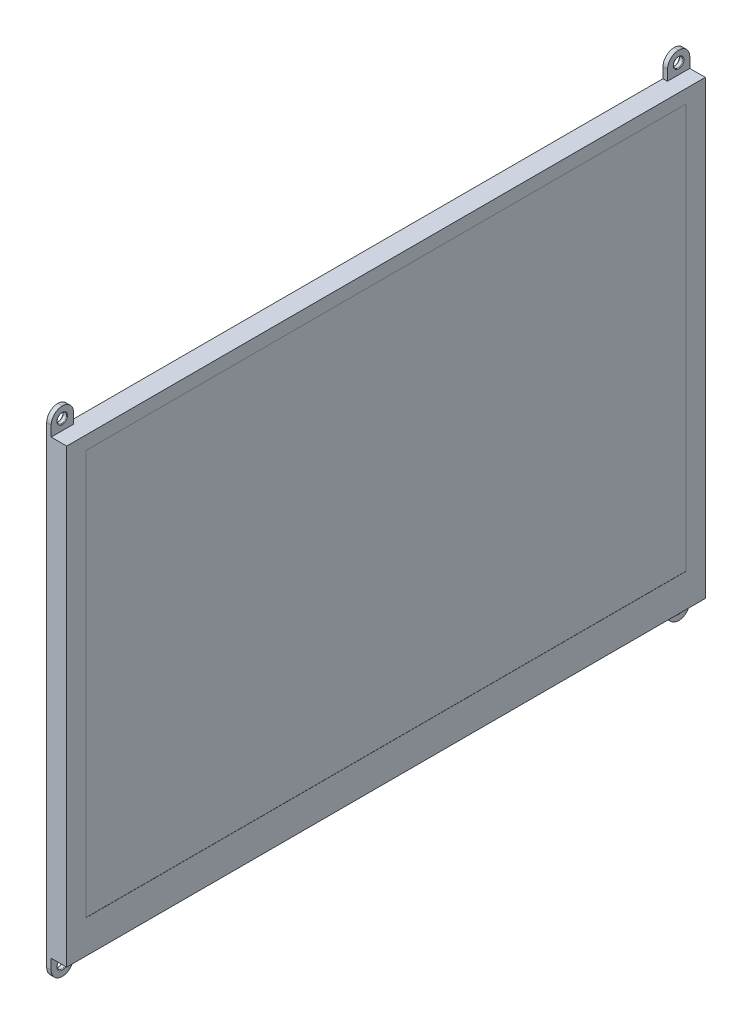
SolidWorks part; units mm, degrees
ref_plane "Front Plane" through (0, 0, 0) normal (1, 0, 0) x (0, 1, 0)
ref_plane "Top Plane" through (0, 0, 0) normal (0, 0, 1) x (0, 1, 0)
ref_plane "Right Plane" through (0, 0, 0) normal (0, 1, 0) x (-1, 0, 0)
sketch "Sketch1" plane through (0, 0, 0) normal (1, 0, 0) x (0, 1, 0)
  line L0 (0, 0) -> (0, 117.475) construction
  line L1 (-83.0199, -117.475) -> (83.0199, -117.475)
  line L2 (-83.0199, -117.475) -> (-83.0199, 117.475)
  line L3 (-83.0199, 117.475) -> (83.0199, 117.475)
  line L4 (83.0199, -117.475) -> (83.0199, 117.475)
  line L5 (-83.0199, -117.475) -> (83.0199, 117.475) construction
  line L6 (-83.0199, 117.475) -> (83.0199, -117.475) construction
  line L7 (83.0199, 117.475) -> (90.8939, 117.475)
  line L8 (83.0199, 117.475) -> (83.0199, 109.2708)
  line L9 (83.0199, 109.2708) -> (90.8939, 109.2708)
  line L10 (90.8939, 117.475) -> (90.8939, 109.2708)
  line L11 (83.0199, 117.475) -> (90.8939, 109.2708) construction
  line L12 (83.0199, 109.2708) -> (90.8939, 117.475) construction
  line L13 (0, 0) -> (83.0199, 0) construction
  line L14 (90.8939, 113.3729) -> (86.8939, 113.3729) construction
  line L15 (-83.0199, -117.475) -> (-83.0199, 117.475)
  line L16 (-83.0199, 117.475) -> (-90.8939, 117.475)
  line L17 (-83.0199, 109.2708) -> (-90.8939, 109.2708)
  line L18 (-90.8939, 117.475) -> (-90.8939, 109.2708)
  line L19 (-83.0199, 117.475) -> (-90.8939, 117.475)
  line L20 (-83.0199, 117.475) -> (-83.0199, 109.2708)
  line L21 (-90.8939, -109.2708) -> (-83.0199, -109.2708)
  line L22 (-90.8939, 117.475) -> (-83.0199, 117.475)
  line L23 (-90.8939, 117.475) -> (-90.8939, 109.2708)
  line L24 (-90.8939, 109.2708) -> (-83.0199, 109.2708)
  line L25 (-83.0199, 117.475) -> (-83.0199, 109.2708)
  line L26 (-90.8939, 117.475) -> (-83.0199, 109.2708) construction
  line L27 (-90.8939, 109.2708) -> (-83.0199, 117.475) construction
  line L28 (-83.0199, -117.475) -> (-83.0199, -109.2708)
  line L29 (-90.8939, -117.475) -> (-83.0199, -117.475)
  line L30 (-90.8939, -117.475) -> (-90.8939, -109.2708)
  line L31 (83.0199, -109.2708) -> (90.8939, -109.2708)
  line L32 (90.8939, -117.475) -> (90.8939, -109.2708)
  line L33 (83.0199, -117.475) -> (90.8939, -117.475)
  line L34 (83.0199, -117.475) -> (83.0199, -109.2708)
  circle A0 centre (86.8939, 113.3729) radius 1.75
  circle A1 centre (-86.8939, 113.3729) radius 1.75
  circle A2 centre (-86.8939, -113.3729) radius 1.75
  circle A3 centre (86.8939, -113.3729) radius 1.75
  point P0 (0, 0)
  point P9 (86.9569, 113.3729)
  point P16 (88.6439, 113.3729)
  point P23 (-86.9569, 113.3729)
  dimension "D5" = 3.5
  dimension "D6" = 2.25
  dimension "D1" = 234.95
  dimension "D2" = 166.0398
  dimension "D3" = 8.2042
  dimension "D4" = 7.874
extrude "Boss-Extrude1" add sketch "Sketch1" along normal blind 1.651 contours L16 L18 L17 L15 A1 | L1 L4 L3 L15 L2 | L10 L7 L4 L9 A0 | L4 L33 L32 L31 A3 | L30 L29 L2 L21 A2 region at (0, 0, 0) region at (0, -86.9569, -117.3613) region at (0, 83.1336, -113.3729) region at (0, -86.9569, 109.3845) region at (0, 83.1336, 113.3729)
sketch "Sketch2" plane through (1.651, 0, 0) normal (1, 0, 0) x (0, 1, 0)
  line L0 (90.8939, 117.475) -> (-90.8939, 117.475) construction
  line L1 (-83.0199, 117.475) -> (83.0199, 117.475)
  line L2 (-83.0199, 117.475) -> (-83.0199, -117.475)
  line L3 (-83.0199, -117.475) -> (83.0199, -117.475)
  line L4 (83.0199, 117.475) -> (83.0199, -117.475)
  line L5 (-83.0199, 117.475) -> (83.0199, -117.475) construction
  line L6 (-83.0199, -117.475) -> (83.0199, 117.475) construction
  line L7 (-90.8939, -117.475) -> (90.8939, -117.475) construction
  point P4 (0, 0)
  point P9 (-83.0199, 109.2708)
  point P10 (79.3869, 117.475)
  line M5 (90.8939, 117.475) -> (-90.8939, 117.475)
  line M8 (-83.0199, 109.2708) -> (-83.0199, -109.2708)
  line M11 (-90.8939, -117.475) -> (90.8939, -117.475)
  line M14 (83.0199, -109.2708) -> (83.0199, 109.2708)
extrude "Boss-Extrude2" add sketch "Sketch2" along normal blind 5.715 contours L4 L2 M5 M8 M11 M14 region at (1.651, 0, 0)
sketch "Sketch3" plane through (7.366, 0, 0) normal (1, 0, 0) x (0, 1, 0)
  line L0 (-83.0199, 117.475) -> (-83.0199, -117.475) construction
  line L1 (-70.8152, -110.363) -> (78.0669, -110.363)
  line L2 (-70.8152, -110.363) -> (-70.8152, 110.363)
  line L3 (-70.8152, 110.363) -> (78.0669, 110.363)
  line L4 (78.0669, -110.363) -> (78.0669, 110.363)
  line L5 (-70.8152, -110.363) -> (78.0669, 110.363) construction
  line L6 (-70.8152, 110.363) -> (78.0669, -110.363) construction
  line L7 (83.0199, 117.475) -> (83.0199, -117.475) construction
  line L8 (-83.0199, -117.475) -> (83.0199, -117.475) construction
  line L9 (83.0199, 117.475) -> (-83.0199, 117.475) construction
  point P4 (3.6259, 0)
  dimension "D1" = 12.2047
  dimension "D2" = 4.953
  dimension "D3" = 7.112
  dimension "D4" = 7.112
extrude "Cut-Extrude1" cut sketch "Sketch3" against normal blind 0.05
fillet "Fillet1" radius 4.1021 8 edges at (0.8255, -90.8939, -117.475) (0.8255, -90.8939, -109.2708) (0.8255, -90.8939, 109.2708) (0.8255, -90.8939, 117.475) (0.8255, 90.8939, 117.475) (0.8255, 90.8939, 109.2708) (0.8255, 90.8939, -109.2708) (0.8255, 90.8939, -117.475)
fillet "Fillet2" radius 0.25 8 edges at (0, -86.8939, 111.6229) (1.651, -86.8939, 111.6229) (0, -86.8939, -115.1229) (1.651, -86.8939, -115.1229) (0, 86.8939, -115.1229) (1.651, 86.8939, -115.1229) (0, 86.8939, 111.6229) (1.651, 86.8939, 111.6229)
